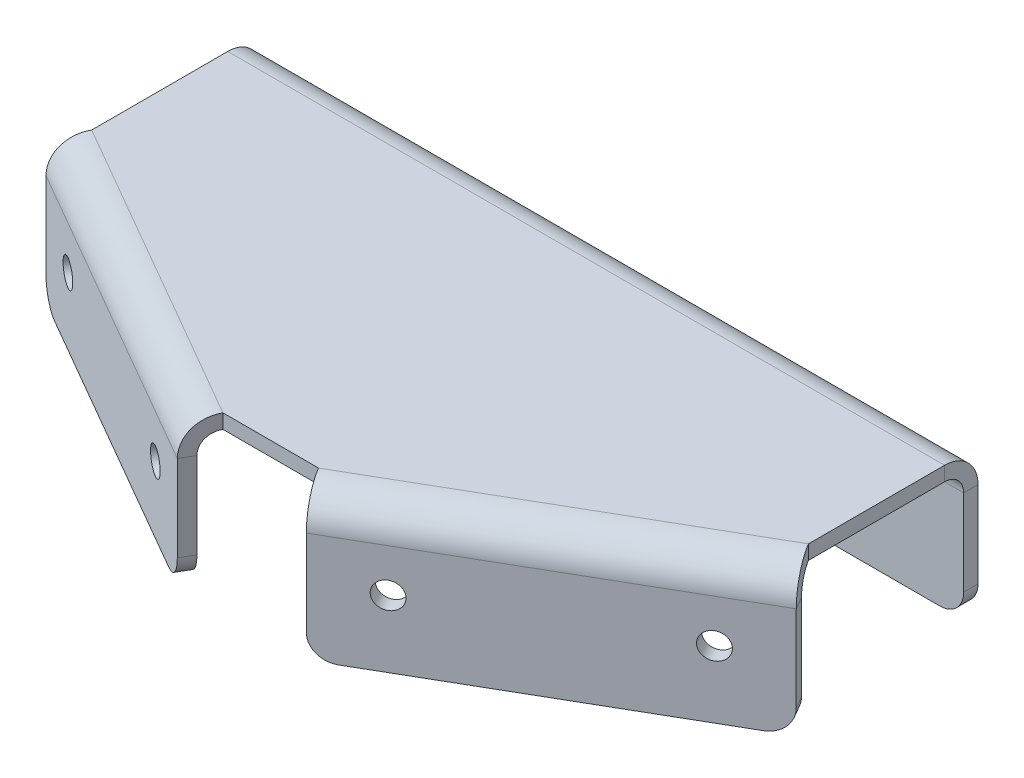
SolidWorks part; units mm, degrees
note: The reader was unsure of these and kept them because the rebuilt part matched: bend radius of "Zgięcie bazowe1"; flange length of "Odgięcie krawędzi1".
material "6063-T1"
ref_plane "Płaszczyzna przednia" through (0, 0, 0) normal (0, 0, 1) x (1, 0, 0)
ref_plane "Płaszczyzna górna" through (0, 0, 0) normal (0, 1, 0) x (1, 0, 0)
ref_plane "Płaszczyzna prawa" through (0, 0, 0) normal (1, 0, 0) x (0, 0, -1)
sketch "Szkic1" plane through (0, 0, 0) normal (1, 0, 0) x (0, 0, -1)
  line L0 (0, -27) -> (0, 0)
  line L1 (0, 0) -> (-70, 0)
  dimension "D1" = 27
  dimension "D2" = 70
base flange "Odgięcie bazowe1" sketch "Szkic1" end condition mid plane depth 150 reverse direction no thickness 3 reverse thickness direction no bend radius 4
bend "Zgięcie bazowe1" bend radius 4 bend angle 90 parameters "D5"=1
sketch "Szkic6" plane through (0, 3, 0) normal (0, 1, 0) x (1, 0, 0)
  line L0 (-75, -32.4722) -> (-10, -70)
  line L1 (-75, -4) -> (-75, -70) construction
  line L2 (75, -70) -> (-75, -70) construction
  line L3 (-10, -70) -> (-75, -70)
  line L4 (-75, -70) -> (-75, -32.4722)
  line L5 (0, 0) -> (0, 50000) construction
  line L6 (75, -70) -> (75, -32.4722)
  line L7 (10, -70) -> (75, -70)
  line L8 (75, -32.4722) -> (10, -70)
  dimension "D1" = 30
  dimension "D2" = 20
extrude "Wytnij-wyciągnięcie1" cut sketch "Szkic6" against normal blind 10 normal cut yes
edge flange "Odgięcie krawędzi1" sketch "Szkic11" flange profiles "Szkic11", "Szkic12" flange angle 90 flange length 30 flange position bend outside bend radius 4 thickness 3 relief rectangular parameters "D6"=10, "D8"=1
sketch "Szkic11" plane through (-32.8109, 0, 56.8301) normal (0.5, 0, -0.866) x (0.866, 0, 0.5)
  line L0 (26.3397, 0) -> (-48.7158, 0) construction
  line L1 (26.3397, 0) -> (-48.7158, 0)
  line L2 (-48.7158, 0) -> (-48.7158, 27)
  line L3 (-48.7158, 27) -> (26.3397, 27)
  line L4 (26.3397, 27) -> (26.3397, 0)
sketch "Szkic12" plane through (32.8109, 0, 56.8301) normal (-0.5, 0, -0.866) x (0.866, 0, -0.5)
  line L0 (48.7158, 0) -> (-26.3397, 0) construction
  line L1 (48.7158, 0) -> (-26.3397, 0)
  line L2 (48.7158, 0) -> (48.7158, 27)
  line L3 (48.7158, 27) -> (-26.3397, 27)
  line L4 (-26.3397, 27) -> (-26.3397, 0)
bend "Zgięcie krawędziowe1" bend radius 4 bend angle 90 parameters "D5"=2
bend "Zgięcie krawędziowe2" bend radius 4 bend angle 90 parameters "D5"=3
hole_wizard "Otwór pod śrubę M52" positions "Szkic13" profile "Szkic14" hole size "M5" standard "ISO"
sketch "Szkic13" plane through (0, 0, -3) normal (0, 0, -1) x (-1, 0, 0)
  line L0 (0, 0) -> (0, 50000) construction
  line L1 (-75, -27) -> (75, -27) construction
  point P0 (-30, -15)
  point P7 (0, 0)
  point P8 (30, -15)
  dimension "D1" = 60
  dimension "D2" = 12
sketch "Szkic14" plane through (30, -15, -3) normal (1, 0, 0) x (0, 1, 0)
  line L0 (0, 0) -> (0, 11.6524)
  line L1 (0, 11.6524) -> (2.75, 10)
  line L2 (2.75, 10) -> (2.75, 0)
  line L5 (2.75, 0) -> (0, 0)
  line L10 (0, 11.6524) -> (-2.75, 10) construction
  line L11 (0, -6.35) -> (0, 107.95) construction
  dimension "Średnica otworu" = 5.5
  dimension "Głębokość otworu" = 10
  dimension "Kąt wiertła" = 118
hole_wizard "Otwór pod śrubę M51" positions "Szkic15" profile "Szkic16" hole size "M5" standard "ISO"
sketch "Szkic15" plane through (-36.3109, 0, 62.8923) normal (-0.5, 0, 0.866) x (0.866, 0, 0.5)
  line L0 (-11.188, -30) -> (-11.188, 49970) construction
  line L1 (26.3397, -27) -> (-48.7158, -27) construction
  point P0 (-36.188, -13)
  point P7 (-11.188, -27)
  point P8 (0, 0)
  point P9 (13.812, -13)
  dimension "D1" = 50
  dimension "D2" = 14
sketch "Szkic16" plane through (-67.6506, -13, 44.7983) normal (0, 1, 0) x (0.866, 0, 0.5)
  line L0 (0, 0) -> (0, 11.6524)
  line L1 (0, 11.6524) -> (2.75, 10)
  line L2 (2.75, 10) -> (2.75, 0)
  line L5 (2.75, 0) -> (0, 0)
  line L10 (0, 11.6524) -> (-2.75, 10) construction
  line L11 (0, -6.35) -> (0, 107.95) construction
  dimension "Średnica otworu" = 5.5
  dimension "Głębokość otworu" = 10
  dimension "Kąt wiertła" = 118
mirror "Lustro1" about plane through (0, 0, 0) normal (1, 0, 0) of "Otwór pod śrubę M51"
fillet "Zaokrąglenie1" radius 5 6 edges at (-77.75, -27, 37.2354) (-12.75, -27, 74.7631) (12.75, -27, 74.7631) (77.75, -27, 37.2354) (75, -27, -1.5) (-75, -27, -1.5)
sketch "Linie zgięcia1" [suppressed] plane through (0, 0, 0) normal (0, 1, 0) x (1, 0, 0)
sketch "Ramka-graniczna1" [suppressed] plane through (0, 0, 0) normal (0, 1, 0) x (1, 0, 0)
sheet metal parameters "Arkusz blachy21" thickness 3 parameters "D1"=4
flat pattern "Rozłożony model21" [suppressed]
sketch "Linie zgięcia2" plane through (0, 0, 0) normal (0, 1, 0) x (1, 0, 0)
sketch "Ramka-graniczna2" [suppressed] plane through (0, 0, 0) normal (0, 1, 0) x (1, 0, 0)
bend of the flat pattern "Rozłożone-<Zgięcie bazowe1>1"
sheet metal parameters "Arkusz blachy22" thickness 3 parameters "D1"=4
flat pattern "Rozłożony model21" [suppressed]
sketch "Linie zgięcia2" plane through (0, 0, 0) normal (0, 1, 0) x (1, 0, 0)
sketch "Ramka-graniczna2" [suppressed] plane through (0, 0, 0) normal (0, 1, 0) x (1, 0, 0)
bend of the flat pattern "Rozłożone-<Zgięcie bazowe1>1"
sheet metal parameters "Arkusz blachy23" thickness 3 parameters "D1"=4
flat pattern "Rozłożony model21" [suppressed]
sketch "Linie zgięcia2" plane through (0, 0, 0) normal (0, 1, 0) x (1, 0, 0)
sketch "Ramka-graniczna2" [suppressed] plane through (0, 0, 0) normal (0, 1, 0) x (1, 0, 0)
bend of the flat pattern "Rozłożone-<Zgięcie bazowe1>1"
bend of the flat pattern "Rozłożone-<Zgięcie krawędziowe1>1"
bend of the flat pattern "Rozłożone-<Zgięcie krawędziowe2>1"
sheet metal parameters "Arkusz blachy24" thickness 3 parameters "D1"=4
flat pattern "Rozłożony model21" [suppressed]
sketch "Linie zgięcia2" plane through (0, 0, 0) normal (0, 1, 0) x (1, 0, 0)
sketch "Ramka-graniczna2" [suppressed] plane through (0, 0, 0) normal (0, 1, 0) x (1, 0, 0)
bend of the flat pattern "Rozłożone-<Zgięcie bazowe1>1"
bend of the flat pattern "Rozłożone-<Zgięcie krawędziowe1>1"
bend of the flat pattern "Rozłożone-<Zgięcie krawędziowe2>1"
sheet metal parameters "Arkusz blachy25" thickness 3 parameters "D1"=4
flat pattern "Rozłożony model21" [suppressed]
sketch "Linie zgięcia2" plane through (0, 0, 0) normal (0, 1, 0) x (1, 0, 0)
sketch "Ramka-graniczna2" [suppressed] plane through (0, 0, 0) normal (0, 1, 0) x (1, 0, 0)
bend of the flat pattern "Rozłożone-<Zgięcie bazowe1>1"
bend of the flat pattern "Rozłożone-<Zgięcie krawędziowe1>1"
bend of the flat pattern "Rozłożone-<Zgięcie krawędziowe2>1"
sheet metal parameters "Arkusz blachy26" thickness 3 parameters "D1"=4
flat pattern "Rozłożony model21"
sketch "Linie zgięcia2" plane through (0, 0, 0) normal (0, -1, 0) x (-1, 0, 0)
  line L0 (-12.1598, -73.741) -> (-77.1598, -36.2132) construction
  line L1 (77.1598, -36.2132) -> (12.1598, -73.741) construction
  line L2 (-75, 0.3197) -> (75, 0.3197) construction
  line L3 (-12.1598, -73.741) -> (-77.1598, -36.2132) construction
  line L4 (77.1598, -36.2132) -> (12.1598, -73.741) construction
  line L5 (-75, 0.3197) -> (75, 0.3197) construction
sketch3d "Ramka-graniczna2" [suppressed]
  line L0 (-13.9895, -95.5703, 0) -> (163.9894, -95.5703, 0) construction
  line L1 (-13.9895, 27.6394, 0) -> (163.9894, 27.6394, 0) construction
  line L2 (-13.9895, -95.5703, 0) -> (-13.9895, 27.6394, 0) construction
  line L3 (163.9894, -95.5703, 0) -> (163.9894, 27.6394, 0) construction
bend of the flat pattern "Rozłożone-<Zgięcie bazowe1>1"
bend of the flat pattern "Rozłożone-<Zgięcie krawędziowe1>1"
bend of the flat pattern "Rozłożone-<Zgięcie krawędziowe2>1"
